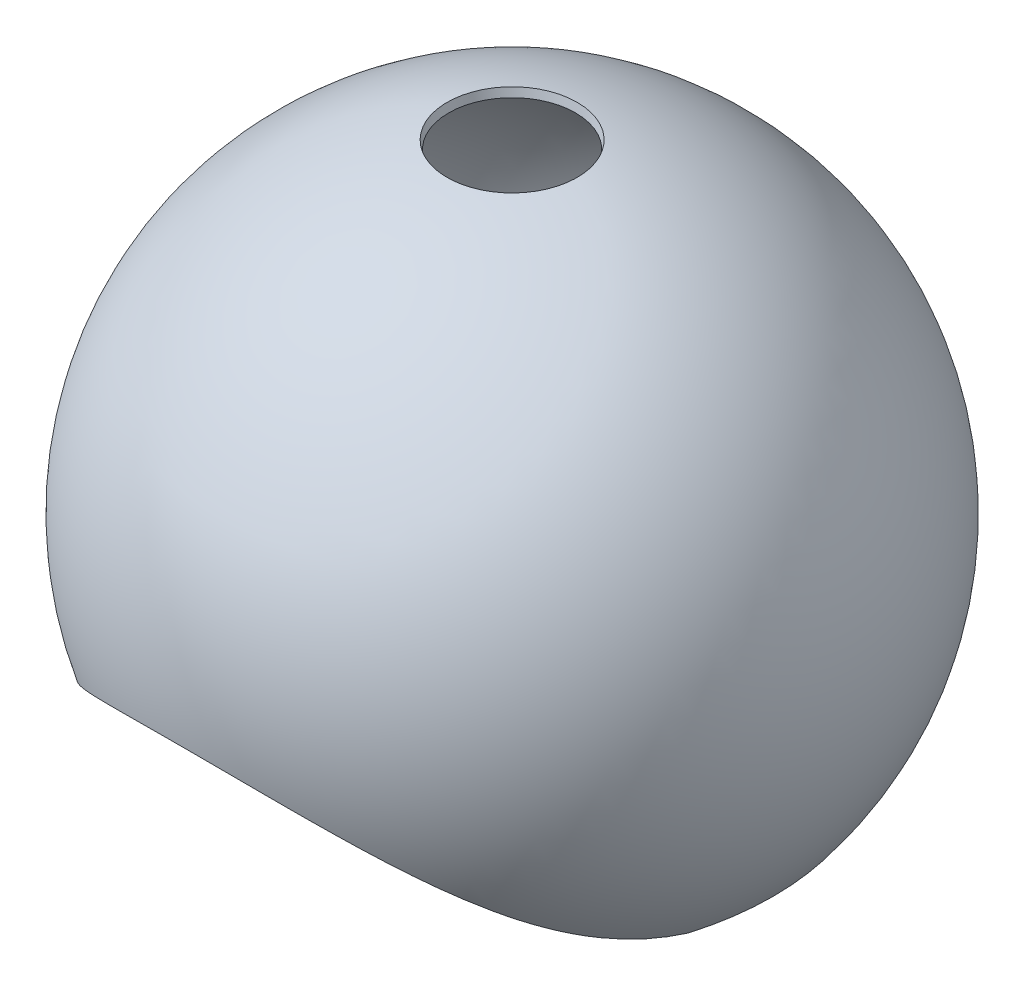
SolidWorks part; units mm, degrees
ref_plane "Front Plane" through (0, 0, 0) normal (0, 0, 1) x (1, 0, 0)
ref_plane "Top Plane" through (0, 0, 0) normal (0, 1, 0) x (1, 0, 0)
ref_plane "Right Plane" through (0, 0, 0) normal (1, 0, 0) x (0, 0, -1)
sketch "Sketch1" plane through (0, 0, 0) normal (0, 0, 1) x (1, 0, 0)
  line L0 (0, 0) -> (0, 78) construction
  line L1 (-61.7509, -47.6532) -> (-59.2045, -47.6532)
  line L3 (-15.3947, 76.4657) -> (-15, 74.505)
  arc A0 (-15.3947, 76.4657) -> (-61.7509, -47.6532) centre (0, 0) ccw
  arc A1 (-15, 74.505) -> (-59.2045, -47.6532) centre (0, 0) ccw
  dimension "D1" = 78
  dimension "D2" = 2
  dimension "D3" = 15
revolve "Revolve1" add sketch "Sketch1" angle 360 about L0
ref_plane "Plane1" through (0, 0, 77) normal (0, 0, 1) x (1, 0, 0)
sketch "Sketch2" plane through (0, 0, 77) normal (0, 0, 1) x (1, 0, 0)
  circle A0 centre (0, 0) radius 5
  dimension "D1" = 10
extrude "Boss-Extrude1" add sketch "Sketch2" against normal blind 10 contours A0
ref_plane "Plane3" through (0, 0, -77) normal (0, 0, 1) x (1, 0, 0)
sketch "Sketch11" plane through (0, 0, -77) normal (0, 0, 1) x (1, 0, 0)
  circle A0 centre (0, 0) radius 5
  dimension "D1" = 10
ref_axis "Axis1" through (0, 76.4657, 0) along (0, -1, 0)
sketch "Sketch5" plane through (0, 0, 67) normal (0, 0, -1) x (-1, 0, 0)
  circle A0 centre (0, 0) radius 2.4
  dimension "D1" = 4.8
extrude "Cut-Extrude2" cut sketch "Sketch5" against normal blind 3
ref_plane "Plane4" through (0, 0, 72) normal (0, 0, -1) x (-1, 0, 0)
sketch "Sketch8" plane through (0, 0, 77) normal (0, 0, 1) x (1, 0, 0)
  line L0 (59.2045, -47.6532) -> (-59.2045, -47.6532)
  line L1 (-61.7509, -47.6532) -> (61.7509, -47.6532) construction
  line L2 (-59.2045, -47.6532) -> (59.2045, -47.6532) construction
  arc A0 (59.2045, -47.6532) -> (-59.2045, -47.6532) centre (0, -74.4828) ccw
  dimension "D1" = 65
extrude "Cut-Extrude5" cut sketch "Sketch8" against normal through all and the other way through all contours A0 L0
sketch "Sketch9" plane through (0, 0, 0) normal (1, 0, 0) x (0, 0, -1)
  line L0 (-24.7996, 42.3678) -> (-18.5037, 44.6594)
  line L1 (-18.5037, 44.6594) -> (-18.5037, 74.505)
  line L3 (-18.5037, 74.505) -> (-27.091, 71.3795)
  line L4 (-27.091, 71.3795) -> (-35.4897, 67.6905)
  line L5 (-35.4897, 67.6905) -> (-39.9781, 64.8692)
  line L6 (-39.9781, 64.8692) -> (-24.7996, 42.3678)
extrude "Boss-Extrude2" add sketch "Sketch9" along normal blind 8 and the other way blind 10 contours L6 L0 L1 L3 L4 L5
sketch "Sketch10" plane through (0, 45.3822, 16.5178) normal (0, -0.9397, -0.342) x (1, 0, 0)
  circle A0 centre (-4.0021, 5.5134) radius 1.4
  circle A1 centre (2.3979, 5.5134) radius 1.4
  dimension "D1" = 2.8
  dimension "D2" = 2.8
extrude "Cut-Extrude6" cut sketch "Sketch10" against normal blind 8
extrude "Boss-Extrude3" add sketch "Sketch11" along normal blind 6
sketch "Sketch12" plane through (0, 0, -71) normal (0, 0, 1) x (1, 0, 0)
  circle A0 centre (0, 0) radius 3
  circle A1 centre (0, 0) radius 5
  dimension "D1" = 10
  dimension "D2" = 6
extrude "Cut-Extrude8" cut sketch "Sketch12" against normal blind 1
sketch "Sketch13" plane through (0, 0, -71) normal (0, 0, 1) x (1, 0, 0)
  circle A0 centre (0, 0) radius 1.9
  dimension "D1" = 3.8
extrude "Cut-Extrude9" cut sketch "Sketch13" against normal blind 5
